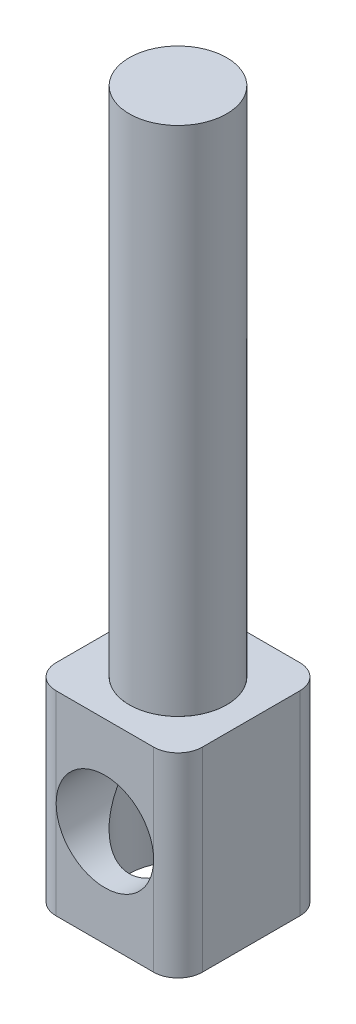
SolidWorks part; units mm, degrees
ref_plane "Front Plane" through (0, 0, 0) normal (0, 0, 1) x (1, 0, 0)
ref_plane "Top Plane" through (0, 0, 0) normal (0, 1, 0) x (1, 0, 0)
ref_plane "Right Plane" through (0, 0, 0) normal (1, 0, 0) x (0, 0, -1)
sketch "Sketch1" plane through (0, 0, 0) normal (0, 1, 0) x (1, 0, 0)
  line L1 (3, -3) -> (-3, -3)
  line L2 (3, -3) -> (3, 3)
  line L3 (3, 3) -> (-3, 3)
  line L4 (-3, -3) -> (-3, 3)
  line L5 (3, -3) -> (-3, 3) construction
  line L6 (3, 3) -> (-3, -3) construction
  circle A0 centre (0, 0) radius 2
  point P0 (0, 0)
  dimension "D2" = 4
  dimension "D1" = 6
extrude "Boss-Extrude1" add sketch "Sketch1" along normal blind 8
sketch "Sketch2" plane through (0, 8, 0) normal (0, 1, 0) x (1, 0, 0)
  circle A1 centre (0, 0) radius 1.9984
  dimension "D1" = 3.9968
extrude "Boss-Extrude2" add sketch "Sketch2" along normal blind 21 separate body
sketch "Sketch3" plane through (0, 0, 3) normal (0, 0, 1) x (1, 0, 0)
  line L0 (0, 8) -> (0, 0) construction
  line L1 (-3, 8) -> (3, 8) construction
  circle A0 centre (0, 4) radius 2
  dimension "D1" = 4
extrude "Cut-Extrude1" cut sketch "Sketch3" against normal blind 3
fillet "Fillet1" radius 1 4 edges at (-3, 4, 3) (-3, 4, -3) (3, 4, -3) (3, 4, 3)
